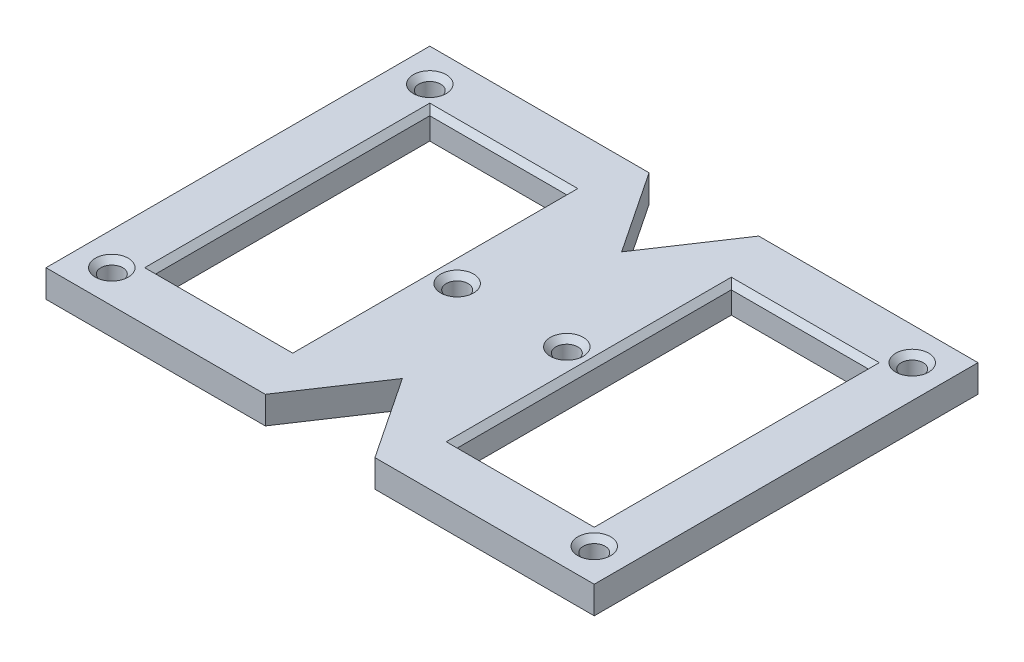
SolidWorks part; units mm, degrees
ref_plane "Alzado" through (0, 0, 0) normal (0, 0, 1) x (1, 0, 0)
ref_plane "Planta" through (0, 0, 0) normal (0, 1, 0) x (1, 0, 0)
ref_plane "Vista lateral" through (0, 0, 0) normal (1, 0, 0) x (0, 0, -1)
sketch "Croquis1" plane through (0, 0, 0) normal (0, 1, 0) x (1, 0, 0)
  line L1 (50, -35) -> (-50, -35)
  line L2 (50, -35) -> (50, 35)
  line L3 (50, 35) -> (-50, 35)
  line L4 (-50, -35) -> (-50, 35)
  line L5 (50, -35) -> (-50, 35) construction
  line L6 (50, 35) -> (-50, -35) construction
  point P0 (0, 0)
  dimension "D1" = 100
  dimension "D2" = 70
extrude "Saliente-Extruir1" add sketch "Croquis1" along normal blind 5
sketch "Croquis3" plane through (0, 5, 0) normal (0, 1, 0) x (1, 0, 0)
  line L0 (50, 35) -> (-50, 35) construction
  line L1 (-44, -29) -> (44, -29) construction
  line L2 (-44, -29) -> (-44, 29) construction
  line L3 (-44, 29) -> (44, 29) construction
  line L4 (44, -29) -> (44, 29) construction
  line L5 (-44, -29) -> (44, 29) construction
  line L6 (-44, 29) -> (44, -29) construction
  line L7 (-50, 35) -> (-50, -35) construction
  circle A0 centre (-44, 29) radius 2
  circle A1 centre (44, 29) radius 2
  circle A2 centre (44, -29) radius 2
  circle A3 centre (-44, -29) radius 2
  point P0 (0, 0)
  dimension "D1" = 4
  dimension "D2" = 6
  dimension "D3" = 6
extrude "Cortar-Extruir2" cut sketch "Croquis3" against normal through all
sketch "Croquis6" plane through (0, 5, 0) normal (0, 1, 0) x (1, 0, 0)
  line L0 (-10, 0) -> (10, 0) construction
  circle A0 centre (-10, 0) radius 2
  circle A1 centre (10, 0) radius 2
  circle A2 centre (-44, 29) radius 2 construction
  dimension "D1" = 10
  dimension "D2" = 10
extrude "Cortar-Extruir3" cut sketch "Croquis6" against normal through all
sketch "Croquis7" plane through (0, 0, 0) normal (0, -1, 0) x (1, 0, 0)
  line L1 (-40, -25) -> (-15, -25)
  line L2 (-40, -25) -> (-40, 25)
  line L3 (-40, 25) -> (-15, 25)
  line L4 (-15, -25) -> (-15, 25)
  line L5 (-40, -25) -> (-15, 25) construction
  line L6 (-40, 25) -> (-15, -25) construction
  line L10 (15, -25) -> (40, -25)
  line L11 (15, -25) -> (15, 25)
  line L12 (15, 25) -> (40, 25)
  line L13 (40, -25) -> (40, 25)
  line L14 (15, -25) -> (40, 25) construction
  line L15 (15, 25) -> (40, -25) construction
  point P0 (-27.5, 0)
  point P7 (27.5, 0)
  dimension "D1" = 15
  dimension "D2" = 15
  dimension "D3" = 40
  dimension "D4" = 40
  dimension "D5" = 25
  dimension "D6" = 25
extrude "Cortar-Extruir4" cut sketch "Croquis7" against normal through all
sketch "Croquis8" plane through (0, 5, 0) normal (0, 1, 0) x (1, 0, 0)
  line L0 (-10, 35) -> (0, 20)
  line L1 (50, 35) -> (-50, 35) construction
  line L2 (0, 20) -> (10, 35)
  line L4 (-10, 35) -> (10, 35)
  line L6 (-10, 0) -> (10, 0) construction
  point P4 (0, 35)
  point P14 (0, 0)
  dimension "D1" = 20
  dimension "D2" = 20
extrude "Cortar-Extruir5" cut sketch "Croquis8" against normal through all
mirror "Simetría1" about plane through (0, 0, 0) normal (0, 0, 1) of "Cortar-Extruir5"
chamfer "Chaflán1" distance 1 angle 45 14 edges at (44, 5, 31) (44, 5, -27) (10, 5, 2) (-10, 5, 2) (-44, 5, 31) (-44, 5, -27) (27.5, 5, 25) (40, 5, 0) (15, 5, 0) (27.5, 5, -25) (-27.5, 5, 25) (-15, 5, 0) (-27.5, 5, -25) (-40, 5, 0)
